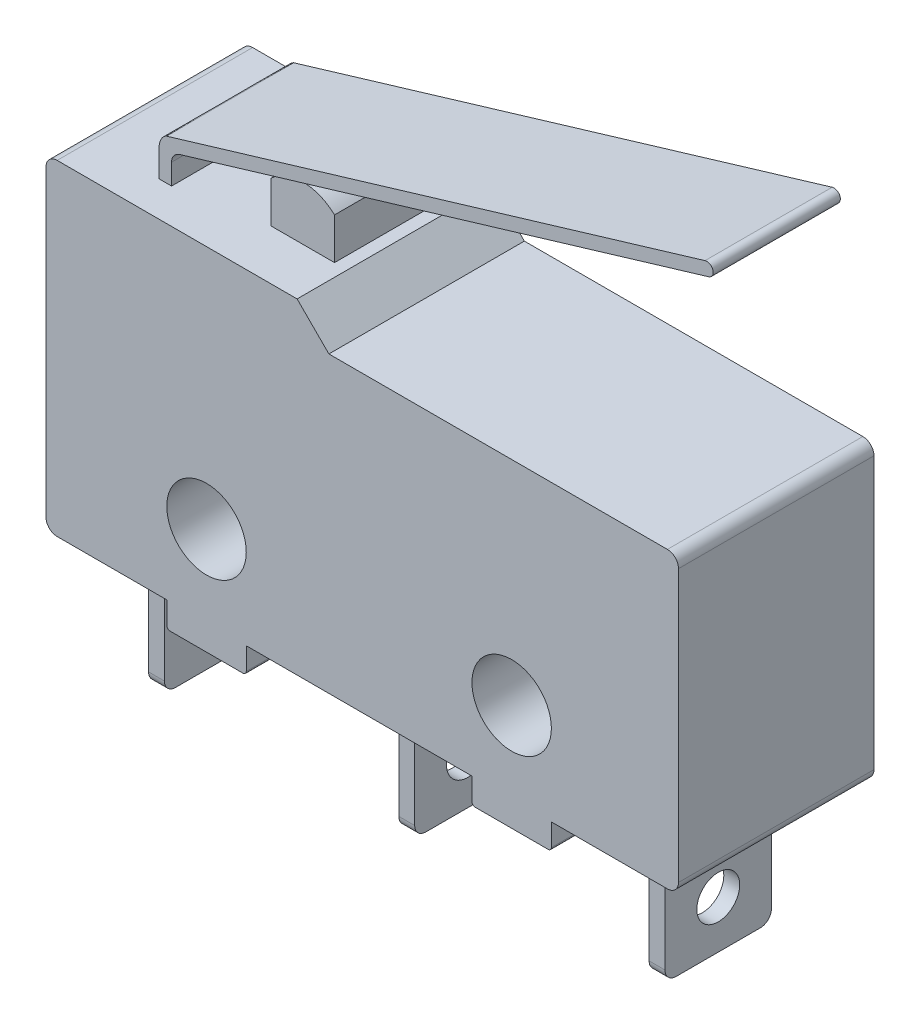
SolidWorks part; units mm, degrees
ref_plane "Front Plane" through (0, 0, 0) normal (0, 0, 1) x (1, 0, 0)
ref_plane "Top Plane" through (0, 0, 0) normal (0, 1, 0) x (1, 0, 0)
ref_plane "Right Plane" through (0, 0, 0) normal (1, 0, 0) x (0, 0, -1)
sketch "Sketch1" plane through (0, 0, 0) normal (0, 0, 1) x (1, 0, 0)
  line L1 (0, 0) -> (19.9, 0)
  line L2 (0, 0) -> (0, 10.25)
  line L3 (0, 10.25) -> (19.9, 10.25)
  line L4 (19.9, 0) -> (19.9, 10.25)
  dimension "D1" = 19.9
  dimension "D2" = 10.25
extrude "Boss-Extrude1" add sketch "Sketch1" along normal blind 6.15
sketch "Sketch2" plane through (0, 0, 6.15) normal (0, 0, 1) x (1, 0, 0)
  line L0 (19.9, 0) -> (19.9, 10.25) construction
  line L1 (7.9, 10.25) -> (19.9, 10.25)
  line L3 (7.9, 9.25) -> (19.9, 9.25)
  line L4 (19.9, 10.25) -> (19.9, 9.25)
  line L5 (7.9, 10.25) -> (7.9, 9.25)
  line L6 (0, 10.25) -> (0, 0) construction
  line L7 (0, 0) -> (19.9, 0) construction
  dimension "D1" = 1
  dimension "D2" = 7.9
  dimension "D3" = 9.25
extrude "Cut-Extrude1" cut sketch "Sketch2" against normal blind 6.15
fillet "Fillet1" radius 1 1 edges at (7.9, 9.25, 3.075) profile chamfer
fillet "Fillet2" radius 0.35 4 edges at (0, 0, 3.075) (19.9, 0, 3.075) (19.9, 9.25, 3.075) (0, 10.25, 3.075)
sketch "Sketch3" plane through (0, 10.25, 0) normal (0, 1, 0) x (1, 0, 0)
  line L0 (0, -6.15) -> (0, 0) construction
  line L1 (5.5, -1.5724) -> (7.5, -1.5724)
  line L2 (5.5, -1.5724) -> (5.5, -4.5724)
  line L3 (5.5, -4.5724) -> (7.5, -4.5724)
  line L4 (7.5, -1.5724) -> (7.5, -4.5724)
  line L5 (0.35, -3.075) -> (8.0134, -3.075) construction
  line L6 (0.35, 0) -> (0.35, -6.15) construction
  line L7 (5.5, -3.0724) -> (7.5, -3.0724) construction
  dimension "D1" = 2
  dimension "D2" = 3
  dimension "D3" = 5.5
extrude "Boss-Extrude2" add sketch "Sketch3" along normal blind 1.7
sketch "Sketch4" plane through (0, 0, 4.5724) normal (0, 0, 1) x (1, 0, 0)
  line L3 (7.5, 11.95) -> (7.5, 10.25) construction
  line L6 (5.5, 11.55) -> (5.5, 11.95)
  line L7 (5.5, 11.95) -> (7.5, 11.95)
  line L8 (7.5, 11.55) -> (7.5, 11.95)
  arc A0 (5.5, 11.55) -> (7.5, 11.55) centre (6.5, 10.5) cw
  point P10 (5.5, 11.55)
  line M2 (7.5, 10.25) -> (7.5, 11.95)
  line M3 (7.5, 11.95) -> (5.5, 11.95)
  line M4 (5.5, 11.95) -> (5.5, 10.25)
extrude "Cut-Extrude2" cut sketch "Sketch4" against normal blind 21.5 contours A0 L7 M4 | A0 M3 M2 region at (7.2574, 11.8335, 4.5724) region at (5.7426, 11.8335, 4.5724)
sketch "Sketch5" plane through (0, 0, 6.15) normal (0, 0, 1) x (1, 0, 0)
  line L0 (0, 9.9) -> (0, 0.35) construction
  line L1 (7.9, 10.25) -> (0.35, 10.25) construction
  line L3 (5.05, 2.55) -> (19.5395, 2.55) construction
  circle A0 centre (5.05, 2.55) radius 1.25
  circle A1 centre (14.65, 2.55) radius 1.25
  point P4 (6.3, 2.55)
  point P5 (13.4, 2.55)
  point P6 (3.8, 2.55)
  point P7 (15.9, 2.55)
  point P10 (5.05, 3.8)
  dimension "D1" = 2.5
  dimension "D2" = 2.5
  dimension "D3" = 7.1
  dimension "D4" = 3.8
  dimension "D5" = 6.45
  dimension "D6" = 0
  dimension "D7" = 14.4895
extrude "Cut-Extrude3" cut sketch "Sketch5" against normal blind 21.5
sketch "Sketch6" plane through (0, 0, 6.15) normal (0, 0, 1) x (1, 0, 0)
  line L0 (0.35, 0) -> (19.55, 0) construction
  line L2 (3.8, 0) -> (3.8, -0.8)
  line L3 (3.8, -0.8) -> (6.3, -0.8)
  line L4 (6.3, 0) -> (6.3, -0.8)
  line L6 (13.4, 0) -> (13.4, -0.8)
  line L7 (13.4, -0.8) -> (15.9, -0.8)
  line L8 (15.9, 0) -> (15.9, -0.8)
  line L9 (3.8, 0) -> (6.3, 0)
  line L10 (13.4, 0) -> (15.9, 0)
  dimension "D1" = 0.8
  dimension "D2" = 0.8
  dimension "D3" = 2.5
  dimension "D5" = 7.1
extrude "Boss-Extrude3" add sketch "Sketch6" against normal blind 6.15
fillet "Fillet3" radius 0.1 4 edges at (15.9, -0.8, 3.075) (13.4, -0.8, 3.075) (3.8, -0.8, 3.075) (6.3, -0.8, 3.075)
sketch "Sketch7" plane through (0, 0, 0) normal (0, -1, 0) x (1, 0, 0)
  line L0 (0.35, 3.075) -> (19.55, 3.075) construction
  line L1 (1.825, 4.75) -> (2.325, 4.75)
  line L2 (1.825, 4.75) -> (1.825, 1.4)
  line L3 (1.825, 1.4) -> (2.325, 1.4)
  line L4 (2.325, 4.75) -> (2.325, 1.4)
  line L5 (0.35, 6.15) -> (0.35, 0) construction
  line L6 (2.075, 6.15) -> (2.075, -1.6097) construction
  line L7 (0.35, 6.15) -> (3.8, 6.15) construction
  line L8 (19.55, 0) -> (19.55, 6.15) construction
  line L9 (9.95, 3.075) -> (9.95, 7.6402) construction
  line L10 (18.075, 1.4) -> (17.575, 1.4)
  line L11 (17.575, 4.75) -> (17.575, 1.4)
  line L12 (18.075, 4.75) -> (17.575, 4.75)
  line L13 (18.075, 4.75) -> (18.075, 1.4)
  line L14 (2.075, 6.15) -> (9.95, 6.15) construction
  line L15 (9.95, 6.15) -> (6.0125, 6.15) construction
  line L16 (6.0125, 6.15) -> (6.0125, 3.075) construction
  line L17 (10.2, 1.4) -> (9.7, 1.4)
  line L18 (10.2, 4.75) -> (9.7, 4.75)
  line L19 (10.2, 4.75) -> (10.2, 1.4)
  line L20 (9.7, 4.75) -> (9.7, 1.4)
  dimension "D1" = 0.5
  dimension "D2" = 3.35
  dimension "D3" = 0.25
  dimension "D4" = 1.675
extrude "Boss-Extrude4" add sketch "Sketch7" along normal blind 4
sketch "Sketch8" plane through (1.825, 0, 0) normal (-1, 0, 0) x (0, 0, 1)
  line L0 (4.75, -4) -> (4.75, 0) construction
  line L2 (4.75, -4) -> (1.4, -4) construction
  circle A0 centre (3.075, -2.5) radius 0.675
  dimension "D1" = 1.35
  dimension "D2" = 1.675
  dimension "D3" = 1.5
extrude "Cut-Extrude4" cut sketch "Sketch8" against normal blind 44
fillet "Fillet4" radius 0.35 6 edges at (17.825, -4, 4.75) (17.825, -4, 1.4) (9.95, -4, 4.75) (9.95, -4, 1.4) (2.075, -4, 1.4) (2.075, -4, 4.75)
sketch "Sketch9" plane through (0, 0, 6.15) normal (0, 0, 1) x (1, 0, 0)
  line L0 (7.9, 10.25) -> (0.35, 10.25) construction
  line L1 (2.45, 10.25) -> (2.85, 10.25)
  line L2 (2.45, 10.25) -> (2.45, 11.25)
  line L3 (2.45, 11.25) -> (2.85, 11.25)
  line L4 (2.85, 10.25) -> (2.85, 11.25)
  line L5 (0, 9.9) -> (0, 0.35) construction
  line L6 (2.45, 11.0015) -> (2.85, 11.117) construction
  line L7 (2.45, 11.25) -> (19.6918, 16.419) construction
  line L16 (2.3926, 11.4416) -> (19.6344, 16.6106)
  line L17 (2.5074, 11.0584) -> (19.7493, 16.2275)
  arc A0 (7.5, 11.55) -> (5.5, 11.55) centre (6.5, 10.5) ccw construction
  arc A2 (2.3926, 11.4416) -> (2.5074, 11.0584) centre (2.45, 11.25) ccw
  arc A3 (19.7493, 16.2275) -> (19.6344, 16.6106) centre (19.6918, 16.419) ccw
  point P6 (2.85, 10.75)
  point P9 (6.5, 11.95)
  point P15 (11.2971, 13.567)
  point P17 (11.0709, 13.8345)
  dimension "D1" = 0.4
  dimension "D2" = 1
  dimension "D3" = 2.45
  dimension "D4" = 0.2
  dimension "D5" = 18
extrude "Boss-Extrude5" add sketch "Sketch9" against normal blind 4 from offset 1.1 contours L17 A3 L16 A2 L2 L3 L4 | L2 L1 L4 L3 region at (11.1399, 13.8563, 6.15) offset against normal yes
sketch "Sketch12" plane through (0, 0, 5.05) normal (0, 0, 1) x (1, 0, 0)
  line L0 (2.3926, 11.4416) -> (19.6344, 16.6106) construction
  line L4 (2.3926, 11.4416) -> (2.6922, 11.5314)
  arc A0 (2.3926, 11.4416) -> (2.45, 11.05) centre (2.45, 11.25) ccw construction
  arc A1 (2.3926, 11.4416) -> (2.45, 11.05) centre (2.45, 11.25) ccw
  spline S0 degree 2 poles (2.45, 11.05) (2.4615, 11.4214) (2.6922, 11.5314) knots 0 0 0 0.80001 0.80001 0.80001
extrude "Cut-Extrude7" cut sketch "Sketch12" against normal blind 24 contours A1 S0 L4
fillet "Fillet6" radius 0.35 1 edges at (2.85, 11.1611, 3.05)
